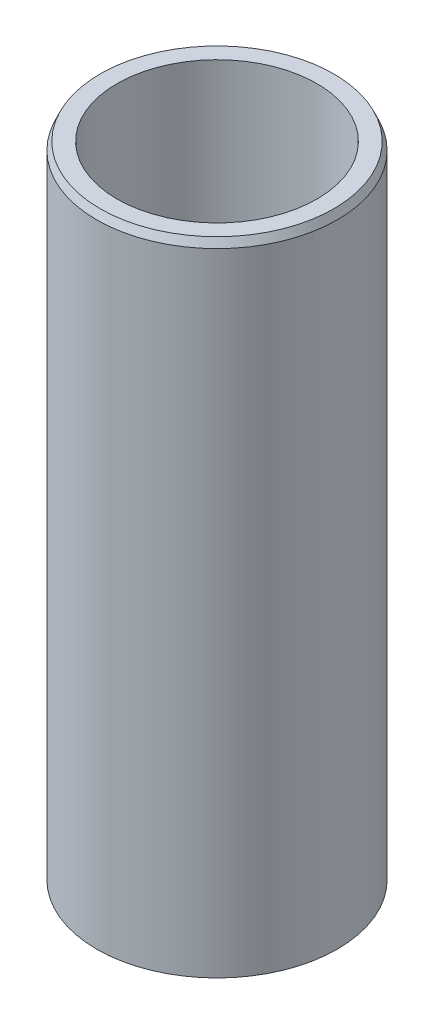
SolidWorks part; units mm, degrees
ref_plane "Front Plane" through (0, 0, 0) normal (0, 0, 1) x (1, 0, 0)
ref_plane "Top Plane" through (0, 0, 0) normal (0, 1, 0) x (1, 0, 0)
ref_plane "Right Plane" through (0, 0, 0) normal (1, 0, 0) x (0, 0, -1)
sketch "Sketch1" plane through (0, 0, 0) normal (0, 1, 0) x (1, 0, 0)
  circle A0 centre (0, 0) radius 55
  dimension "SHAFT_OD" = 110
extrude "Boss-Extrude1" add sketch "Sketch1" along normal blind 293.9547
sketch "Sketch2" plane through (0, 0, 0) normal (0, 1, 0) x (1, 0, 0)
  circle A0 centre (0, 0) radius 45.7149
  dimension "BORE_D" = 91.4298
extrude "Cut-Extrude1" cut sketch "Sketch2" along normal through all
chamfer "Chamfer1" distance 3.5995 angle 23.749 2 edges at (0, 293.9547, 55) (0, 0, 55) first distance on face at (0, 293.9547, 55) first distance on face at (0, 0, 45.7149)
